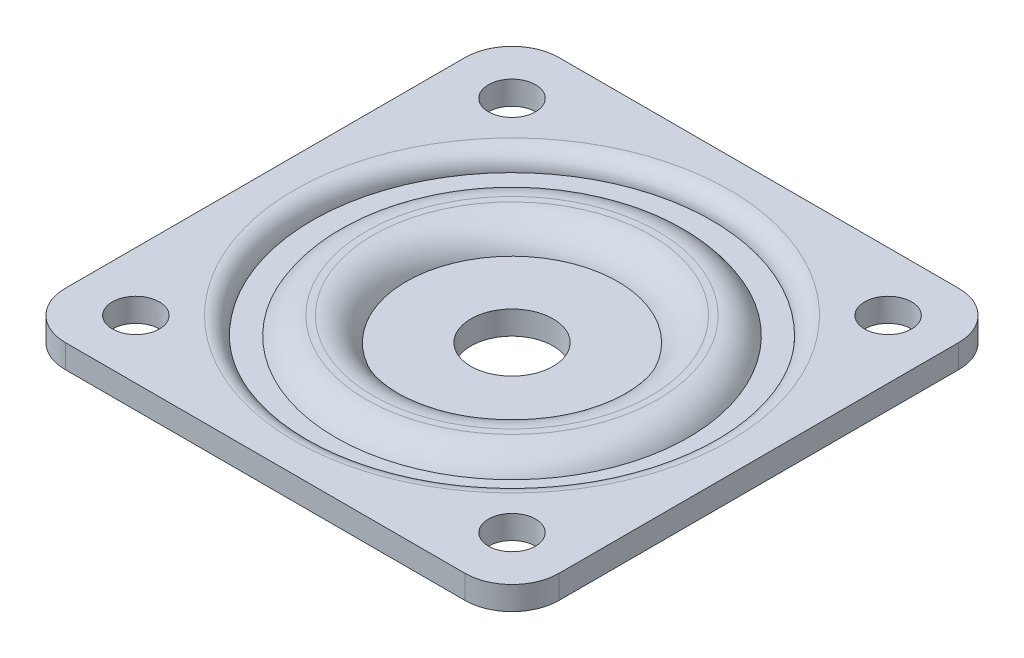
SolidWorks part; units mm, degrees
ref_plane "Plano frontal" through (0, 0, 0) normal (0, 0, 1) x (1, 0, 0)
ref_plane "Plano superior" through (0, 0, 0) normal (0, 1, 0) x (1, 0, 0)
ref_plane "Plano direito" through (0, 0, 0) normal (1, 0, 0) x (0, 0, -1)
sketch "Esboço9" plane through (0, 0, 0) normal (0, 1, 0) x (1, 0, 0)
  line L1 (21, -21) -> (-21, -21)
  line L2 (21, -21) -> (21, 21)
  line L3 (21, 21) -> (-21, 21)
  line L4 (-21, -21) -> (-21, 21)
  line L5 (21, -21) -> (-21, 21) construction
  line L6 (21, 21) -> (-21, -21) construction
  point P0 (0, 0)
  dimension "D1" = 42
  dimension "D2" = 42
extrude "Ressalto-extrusão1" add sketch "Esboço9" along normal blind 4
sketch "Esboço10" plane through (0, 4, 0) normal (0, 1, 0) x (1, 0, 0)
  circle A0 centre (0, 0) radius 15
  circle A1 centre (0, 0) radius 17
  dimension "D1" = 30
  dimension "D2" = 2
extrude "Corte-extrusão1" cut sketch "Esboço10" against normal blind 1.5
fillet "Filete1" radius 1.5 1 edges at (0, 4, 17)
sketch "Esboço11" plane through (0, 0, 0) normal (0, -1, 0) x (1, 0, 0)
  line L1 (-21, 21) -> (21, 21)
  line L2 (-21, 21) -> (-21, -21)
  line L3 (-21, -21) -> (21, -21)
  line L4 (21, 21) -> (21, -21)
  circle A0 centre (0, 0) radius 15
  circle A1 centre (0, 0) radius 17
  line M1 (-21, 21) -> (-21, -21)
  line M2 (-21, -21) -> (21, -21)
  line M3 (21, -21) -> (21, 21)
  line M4 (21, 21) -> (-21, 21)
  dimension "D1" = 30
  dimension "D2" = 2
extrude "Corte-extrusão2" cut sketch "Esboço11" against normal blind 2 contours A1 M4 M1 M2 M3 region at (0, 0, 20.406)
fillet "Filete2" radius 2 1 edges at (0, 0, -17)
sketch "Esboço12" plane through (0, 4, 0) normal (0, 1, 0) x (1, 0, 0)
  circle A0 centre (0, 0) radius 9
  dimension "D1" = 18
extrude "Corte-extrusão3" cut sketch "Esboço12" against normal blind 2
fillet "Filete3" radius 3 2 edges at (0, 4, 9) (0, 4, 15)
sketch "Esboço13" plane through (0, 0, 0) normal (0, -1, 0) x (1, 0, 0)
  circle A0 centre (0, 0) radius 14
  circle A1 centre (0, 0) radius 12
  dimension "D1" = 28
  dimension "D2" = 2
extrude "Corte-extrusão4" cut sketch "Esboço13" against normal blind 2
fillet "Filete4" radius 2 2 edges at (0, 0, -12) (0, 0, -14)
sketch "Esboço14" plane through (0, 2, 0) normal (0, 1, 0) x (1, 0, 0)
  circle A0 centre (0, 0) radius 3.5
  dimension "D1" = 7
extrude "Corte-extrusão5" cut sketch "Esboço14" against normal through all
hole_wizard "Furo de diâmetro Ø5.0 (5)1" positions "Esboço17" profile "Esboço16" hole size "Ø5.0" standard "ISO" end condition through all
sketch "Esboço17" plane through (0, 4, 0) normal (0, 1, 0) x (1, 0, 0)
  circle A0 centre (0, 0) radius 3.5 construction
  point P0 (-16, -16)
  point P2 (-16, 16)
  point P4 (16, 16)
  point P6 (16, -16)
  dimension "D1" = 32
  dimension "D2" = 32
  dimension "D3" = 32
  dimension "D4" = 32
  dimension "D5" = 16
  dimension "D6" = 16
sketch "Esboço16" plane through (-16, 4, 16) normal (1, 0, 0) x (0, 0, 1)
  line L0 (0, 0) -> (0, 4)
  line L1 (0, 4) -> (2, 4)
  line L2 (2, 4) -> (2, 0)
  line L5 (2, 0) -> (0, 0)
  line L11 (0, -6.35) -> (0, 107.95) construction
  dimension "Thru Hole Dia." = 4
  dimension "Thru Hole Depth" = 4
fillet "Filete5" radius 4 4 edges at (-21, 3, -21) (21, 3, -21) (21, 3, 21) (-21, 3, 21)
